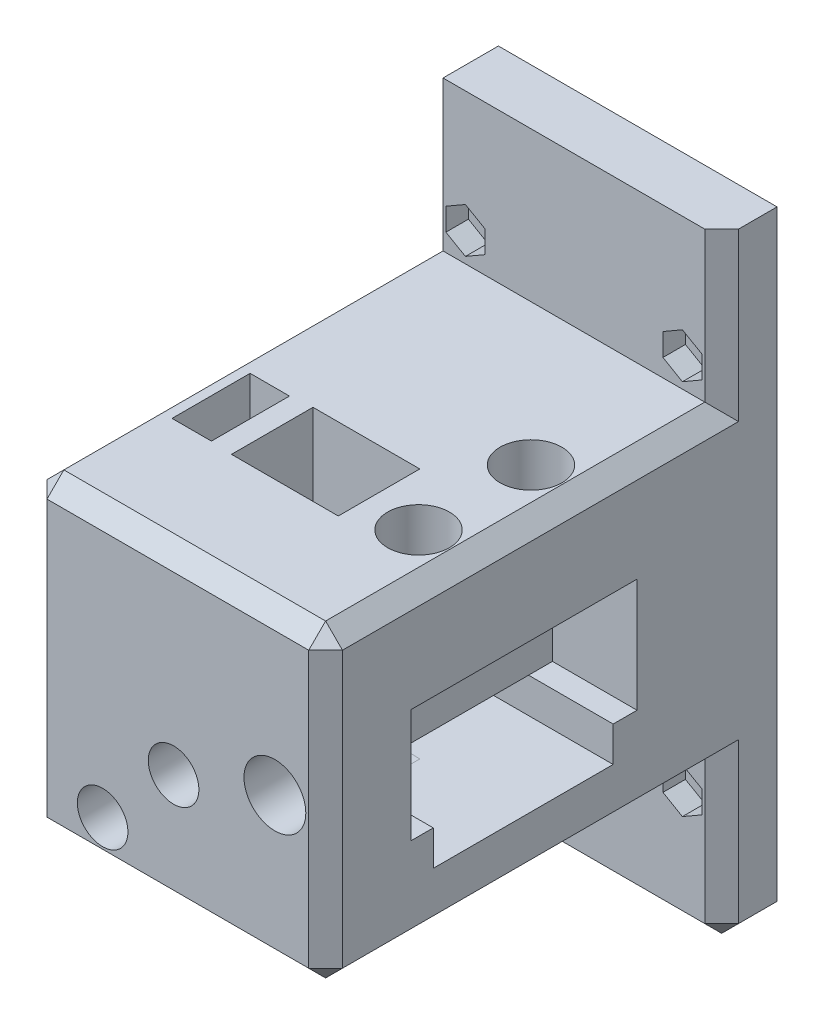
SolidWorks part; units mm, degrees
ref_plane "Front Plane" through (0, 0, 0) normal (1, 0, 0) x (0, 1, 0)
ref_plane "Top Plane" through (0, 0, 0) normal (0, 0, 1) x (0, 1, 0)
ref_plane "Right Plane" through (0, 0, 0) normal (0, 1, 0) x (-1, 0, 0)
sketch "Sketch1" plane through (0, 0, 0) normal (1, 0, 0) x (0, 1, 0)
  line L0 (-10.15, 6.7) -> (-10.15, -6.7)
  line L1 (-9.2, -7.65) -> (-8.5, -7.65)
  line L2 (-8.05, -7.2) -> (-8.05, -5.0949)
  line L3 (-6.8637, -4.6035) -> (-4.6847, -6.7825)
  line L4 (-3.85, -8.7978) -> (-3.85, -11.2022)
  line L5 (-4.6847, -13.2175) -> (-6.8637, -15.3965)
  line L6 (-8.05, -14.9051) -> (-8.05, -12.8)
  line L7 (-8.5, -12.35) -> (-9.2, -12.35)
  line L8 (-10.15, -13.3) -> (-10.15, -18)
  line L9 (-8, -20.15) -> (-3.3, -20.15)
  line L10 (-2.35, -19.2) -> (-2.35, -18.5)
  line L11 (-2.8, -18.05) -> (-4.9051, -18.05)
  line L12 (-5.3965, -16.8637) -> (-3.2175, -14.6847)
  line L13 (-1.2022, -13.85) -> (1.2022, -13.85)
  line L14 (3.2175, -14.6847) -> (5.3965, -16.8637)
  line L15 (4.9051, -18.05) -> (2.8, -18.05)
  line L16 (2.35, -18.5) -> (2.35, -19.2)
  line L17 (3.3, -20.15) -> (8, -20.15)
  line L18 (10.15, -18) -> (10.15, -13.3)
  line L19 (9.2, -12.35) -> (8.5, -12.35)
  line L20 (8.05, -12.8) -> (8.05, -14.9051)
  line L21 (6.8637, -15.3965) -> (4.6847, -13.2175)
  line L22 (3.85, -11.2022) -> (3.85, -8.7978)
  line L23 (4.6847, -6.7825) -> (6.8637, -4.6035)
  line L24 (8.05, -5.0949) -> (8.05, -7.2)
  line L25 (8.5, -7.65) -> (9.2, -7.65)
  line L26 (10.15, -6.7) -> (10.15, 6.7)
  line L27 (9.2, 7.65) -> (8.5, 7.65)
  line L28 (8.05, 7.2) -> (8.05, 5.0949)
  line L29 (6.8637, 4.6035) -> (4.6847, 6.7825)
  line L30 (3.85, 8.7978) -> (3.85, 11.2022)
  line L31 (4.6847, 13.2175) -> (6.8637, 15.3965)
  line L32 (8.05, 14.9051) -> (8.05, 12.8)
  line L33 (8.5, 12.35) -> (9.2, 12.35)
  line L34 (10.15, 13.3) -> (10.15, 18)
  line L35 (8, 20.15) -> (3.3, 20.15)
  line L36 (2.35, 19.2) -> (2.35, 18.5)
  line L37 (2.8, 18.05) -> (4.9051, 18.05)
  line L38 (5.3965, 16.8637) -> (3.2175, 14.6847)
  line L39 (1.2022, 13.85) -> (-1.2022, 13.85)
  line L40 (-3.2175, 14.6847) -> (-5.3965, 16.8637)
  line L41 (-4.9051, 18.05) -> (-2.8, 18.05)
  line L42 (-2.35, 18.5) -> (-2.35, 19.2)
  line L43 (-3.3, 20.15) -> (-8, 20.15)
  line L44 (-10.15, 18) -> (-10.15, 13.3)
  line L45 (-9.2, 12.35) -> (-8.5, 12.35)
  line L46 (-8.05, 12.8) -> (-8.05, 14.9051)
  line L47 (-6.8637, 15.3965) -> (-4.6847, 13.2175)
  line L48 (-3.85, 11.2022) -> (-3.85, 8.7978)
  line L49 (-4.6847, 6.7825) -> (-6.8637, 4.6035)
  line L50 (-8.05, 5.0949) -> (-8.05, 7.2)
  line L51 (-8.5, 7.65) -> (-9.2, 7.65)
  line L52 (-2.5, 18.5) -> (-2.5, 19.2)
  line L53 (-3.3, 20) -> (-8, 20)
  line L54 (-10, 18) -> (-10, 13.3)
  line L55 (-9.2, 12.5) -> (-8.5, 12.5)
  line L56 (-8.2, 12.8) -> (-8.2, 14.9051)
  line L57 (-6.7576, 15.5025) -> (-4.5787, 13.3236)
  line L58 (-3.7, 11.2022) -> (-3.7, 8.7978)
  line L59 (-4.5787, 6.6764) -> (-6.7576, 4.4975)
  line L60 (-8.2, 5.0949) -> (-8.2, 7.2)
  line L61 (-8.5, 7.5) -> (-9.2, 7.5)
  line L62 (-10, 6.7) -> (-10, -6.7)
  line L63 (-9.2, -7.5) -> (-8.5, -7.5)
  line L64 (-8.2, -7.2) -> (-8.2, -5.0949)
  line L65 (-6.7576, -4.4975) -> (-4.5787, -6.6764)
  line L66 (-3.7, -8.7978) -> (-3.7, -11.2022)
  line L67 (-4.5787, -13.3236) -> (-6.7576, -15.5025)
  line L68 (-8.2, -14.9051) -> (-8.2, -12.8)
  line L69 (-8.5, -12.5) -> (-9.2, -12.5)
  line L70 (-10, -13.3) -> (-10, -18)
  line L71 (-8, -20) -> (-3.3, -20)
  line L72 (-2.5, -19.2) -> (-2.5, -18.5)
  line L73 (-2.8, -18.2) -> (-4.9051, -18.2)
  line L74 (-5.5025, -16.7576) -> (-3.3236, -14.5787)
  line L75 (-1.2022, -13.7) -> (1.2022, -13.7)
  line L76 (3.3236, -14.5787) -> (5.5025, -16.7576)
  line L77 (4.9051, -18.2) -> (2.8, -18.2)
  line L78 (2.5, -18.5) -> (2.5, -19.2)
  line L79 (3.3, -20) -> (8, -20)
  line L80 (10, -18) -> (10, -13.3)
  line L81 (9.2, -12.5) -> (8.5, -12.5)
  line L82 (8.2, -12.8) -> (8.2, -14.9051)
  line L83 (6.7576, -15.5025) -> (4.5787, -13.3236)
  line L84 (3.7, -11.2022) -> (3.7, -8.7978)
  line L85 (4.5787, -6.6764) -> (6.7576, -4.4975)
  line L86 (8.2, -5.0949) -> (8.2, -7.2)
  line L87 (8.5, -7.5) -> (9.2, -7.5)
  line L88 (10, -6.7) -> (10, 6.7)
  line L89 (9.2, 7.5) -> (8.5, 7.5)
  line L90 (8.2, 7.2) -> (8.2, 5.0949)
  line L91 (6.7576, 4.4975) -> (4.5787, 6.6764)
  line L92 (3.7, 8.7978) -> (3.7, 11.2022)
  line L93 (4.5787, 13.3236) -> (6.7576, 15.5025)
  line L94 (8.2, 14.9051) -> (8.2, 12.8)
  line L95 (8.5, 12.5) -> (9.2, 12.5)
  line L96 (10, 13.3) -> (10, 18)
  line L97 (8, 20) -> (3.3, 20)
  line L98 (2.5, 19.2) -> (2.5, 18.5)
  line L99 (2.8, 18.2) -> (4.9051, 18.2)
  line L100 (5.5025, 16.7576) -> (3.3236, 14.5787)
  line L101 (1.2022, 13.7) -> (-1.2022, 13.7)
  line L102 (-3.3236, 14.5787) -> (-5.5025, 16.7576)
  line L103 (-4.9051, 18.2) -> (-2.8, 18.2)
  line L104 (-2.5, 18.5) -> (-2.5, 19.2)
  line L105 (-3.3, 20) -> (-8, 20)
  line L106 (-10, 18) -> (-10, 13.3)
  line L107 (-9.2, 12.5) -> (-8.5, 12.5)
  line L108 (-8.2, 12.8) -> (-8.2, 14.9051)
  line L109 (-6.7576, 15.5025) -> (-4.5787, 13.3236)
  line L110 (-3.7, 11.2022) -> (-3.7, 8.7978)
  line L111 (-4.5787, 6.6764) -> (-6.7576, 4.4975)
  line L112 (-8.2, 5.0949) -> (-8.2, 7.2)
  line L113 (-8.5, 7.5) -> (-9.2, 7.5)
  line L114 (-10, 6.7) -> (-10, -6.7)
  line L115 (-9.2, -7.5) -> (-8.5, -7.5)
  line L116 (-8.2, -7.2) -> (-8.2, -5.0949)
  line L117 (-6.7576, -4.4975) -> (-4.5787, -6.6764)
  line L118 (-3.7, -8.7978) -> (-3.7, -11.2022)
  line L119 (-4.5787, -13.3236) -> (-6.7576, -15.5025)
  line L120 (-8.2, -14.9051) -> (-8.2, -12.8)
  line L121 (-8.5, -12.5) -> (-9.2, -12.5)
  line L122 (-10, -13.3) -> (-10, -18)
  line L123 (-8, -20) -> (-3.3, -20)
  line L124 (-2.5, -19.2) -> (-2.5, -18.5)
  line L125 (-2.8, -18.2) -> (-4.9051, -18.2)
  line L126 (-5.5025, -16.7576) -> (-3.3236, -14.5787)
  line L127 (-1.2022, -13.7) -> (1.2022, -13.7)
  line L128 (3.3236, -14.5787) -> (5.5025, -16.7576)
  line L129 (4.9051, -18.2) -> (2.8, -18.2)
  line L130 (2.5, -18.5) -> (2.5, -19.2)
  line L131 (3.3, -20) -> (8, -20)
  line L132 (10, -18) -> (10, -13.3)
  line L133 (9.2, -12.5) -> (8.5, -12.5)
  line L134 (8.2, -12.8) -> (8.2, -14.9051)
  line L135 (6.7576, -15.5025) -> (4.5787, -13.3236)
  line L136 (3.7, -11.2022) -> (3.7, -8.7978)
  line L137 (4.5787, -6.6764) -> (6.7576, -4.4975)
  line L138 (8.2, -5.0949) -> (8.2, -7.2)
  line L139 (8.5, -7.5) -> (9.2, -7.5)
  line L140 (10, -6.7) -> (10, 6.7)
  line L141 (9.2, 7.5) -> (8.5, 7.5)
  line L142 (8.2, 7.2) -> (8.2, 5.0949)
  line L143 (6.7576, 4.4975) -> (4.5787, 6.6764)
  line L144 (3.7, 8.7978) -> (3.7, 11.2022)
  line L145 (4.5787, 13.3236) -> (6.7576, 15.5025)
  line L146 (8.2, 14.9051) -> (8.2, 12.8)
  line L147 (8.5, 12.5) -> (9.2, 12.5)
  line L148 (10, 13.3) -> (10, 18)
  line L149 (8, 20) -> (3.3, 20)
  line L150 (2.5, 19.2) -> (2.5, 18.5)
  line L151 (2.8, 18.2) -> (4.9051, 18.2)
  line L152 (5.5025, 16.7576) -> (3.3236, 14.5787)
  line L153 (1.2022, 13.7) -> (-1.2022, 13.7)
  line L154 (-3.3236, 14.5787) -> (-5.5025, 16.7576)
  line L155 (-4.9051, 18.2) -> (-2.8, 18.2)
  line L156 (55, -61.229) -> (55, -45) construction
  line L157 (17.15, 35.15) -> (-17.15, 35.15)
  line L158 (17.15, 35.15) -> (17.15, -35.15)
  line L159 (17.15, -35.15) -> (-17.15, -35.15)
  line L160 (-17.15, 35.15) -> (-17.15, -35.15)
  line L161 (17.15, 35.15) -> (-17.15, -35.15) construction
  line L162 (17.15, -35.15) -> (-17.15, 35.15) construction
  line L163 (-55, -45) -> (55, -45)
  line L164 (-55, -45) -> (-55, -35.15)
  line L165 (-55, -35.15) -> (55, -35.15)
  line L166 (55, -45) -> (55, -35.15)
  arc A0 (-10.15, -6.7) -> (-9.2, -7.65) centre (-9.2, -6.7) ccw
  arc A1 (-8.5, -7.65) -> (-8.05, -7.2) centre (-8.5, -7.2) ccw
  arc A2 (-6.8637, -4.6035) -> (-8.05, -5.0949) centre (-7.3551, -5.0949) ccw
  arc A3 (-3.85, -8.7978) -> (-4.6847, -6.7825) centre (-6.7, -8.7978) ccw
  arc A4 (-4.6847, -13.2175) -> (-3.85, -11.2022) centre (-6.7, -11.2022) ccw
  arc A5 (-8.05, -14.9051) -> (-6.8637, -15.3965) centre (-7.3551, -14.9051) ccw
  arc A6 (-8.05, -12.8) -> (-8.5, -12.35) centre (-8.5, -12.8) ccw
  arc A7 (-9.2, -12.35) -> (-10.15, -13.3) centre (-9.2, -13.3) ccw
  arc A8 (-10.15, -18) -> (-8, -20.15) centre (-8, -18) ccw
  arc A9 (-3.3, -20.15) -> (-2.35, -19.2) centre (-3.3, -19.2) ccw
  arc A10 (-2.35, -18.5) -> (-2.8, -18.05) centre (-2.8, -18.5) ccw
  arc A11 (-5.3965, -16.8637) -> (-4.9051, -18.05) centre (-4.9051, -17.3551) ccw
  arc A12 (-1.2022, -13.85) -> (-3.2175, -14.6847) centre (-1.2022, -16.7) ccw
  arc A13 (3.2175, -14.6847) -> (1.2022, -13.85) centre (1.2022, -16.7) ccw
  arc A14 (4.9051, -18.05) -> (5.3965, -16.8637) centre (4.9051, -17.3551) ccw
  arc A15 (2.8, -18.05) -> (2.35, -18.5) centre (2.8, -18.5) ccw
  arc A16 (2.35, -19.2) -> (3.3, -20.15) centre (3.3, -19.2) ccw
  arc A17 (8, -20.15) -> (10.15, -18) centre (8, -18) ccw
  arc A18 (10.15, -13.3) -> (9.2, -12.35) centre (9.2, -13.3) ccw
  arc A19 (8.5, -12.35) -> (8.05, -12.8) centre (8.5, -12.8) ccw
  arc A20 (6.8637, -15.3965) -> (8.05, -14.9051) centre (7.3551, -14.9051) ccw
  arc A21 (3.85, -11.2022) -> (4.6847, -13.2175) centre (6.7, -11.2022) ccw
  arc A22 (4.6847, -6.7825) -> (3.85, -8.7978) centre (6.7, -8.7978) ccw
  arc A23 (8.05, -5.0949) -> (6.8637, -4.6035) centre (7.3551, -5.0949) ccw
  arc A24 (8.05, -7.2) -> (8.5, -7.65) centre (8.5, -7.2) ccw
  arc A25 (9.2, -7.65) -> (10.15, -6.7) centre (9.2, -6.7) ccw
  arc A26 (10.15, 6.7) -> (9.2, 7.65) centre (9.2, 6.7) ccw
  arc A27 (8.5, 7.65) -> (8.05, 7.2) centre (8.5, 7.2) ccw
  arc A28 (6.8637, 4.6035) -> (8.05, 5.0949) centre (7.3551, 5.0949) ccw
  arc A29 (3.85, 8.7978) -> (4.6847, 6.7825) centre (6.7, 8.7978) ccw
  arc A30 (4.6847, 13.2175) -> (3.85, 11.2022) centre (6.7, 11.2022) ccw
  arc A31 (8.05, 14.9051) -> (6.8637, 15.3965) centre (7.3551, 14.9051) ccw
  arc A32 (8.05, 12.8) -> (8.5, 12.35) centre (8.5, 12.8) ccw
  arc A33 (9.2, 12.35) -> (10.15, 13.3) centre (9.2, 13.3) ccw
  arc A34 (10.15, 18) -> (8, 20.15) centre (8, 18) ccw
  arc A35 (3.3, 20.15) -> (2.35, 19.2) centre (3.3, 19.2) ccw
  arc A36 (2.35, 18.5) -> (2.8, 18.05) centre (2.8, 18.5) ccw
  arc A37 (5.3965, 16.8637) -> (4.9051, 18.05) centre (4.9051, 17.3551) ccw
  arc A38 (1.2022, 13.85) -> (3.2175, 14.6847) centre (1.2022, 16.7) ccw
  arc A39 (-3.2175, 14.6847) -> (-1.2022, 13.85) centre (-1.2022, 16.7) ccw
  arc A40 (-4.9051, 18.05) -> (-5.3965, 16.8637) centre (-4.9051, 17.3551) ccw
  arc A41 (-2.8, 18.05) -> (-2.35, 18.5) centre (-2.8, 18.5) ccw
  arc A42 (-2.35, 19.2) -> (-3.3, 20.15) centre (-3.3, 19.2) ccw
  arc A43 (-8, 20.15) -> (-10.15, 18) centre (-8, 18) ccw
  arc A44 (-10.15, 13.3) -> (-9.2, 12.35) centre (-9.2, 13.3) ccw
  arc A45 (-8.5, 12.35) -> (-8.05, 12.8) centre (-8.5, 12.8) ccw
  arc A46 (-6.8637, 15.3965) -> (-8.05, 14.9051) centre (-7.3551, 14.9051) ccw
  arc A47 (-3.85, 11.2022) -> (-4.6847, 13.2175) centre (-6.7, 11.2022) ccw
  arc A48 (-4.6847, 6.7825) -> (-3.85, 8.7978) centre (-6.7, 8.7978) ccw
  arc A49 (-8.05, 5.0949) -> (-6.8637, 4.6035) centre (-7.3551, 5.0949) ccw
  arc A50 (-8.05, 7.2) -> (-8.5, 7.65) centre (-8.5, 7.2) ccw
  arc A51 (-9.2, 7.65) -> (-10.15, 6.7) centre (-9.2, 6.7) ccw
  arc A52 (-2.8, 18.2) -> (-2.5, 18.5) centre (-2.8, 18.5) ccw
  arc A53 (-2.5, 19.2) -> (-3.3, 20) centre (-3.3, 19.2) ccw
  arc A54 (-8, 20) -> (-10, 18) centre (-8, 18) ccw
  arc A55 (-10, 13.3) -> (-9.2, 12.5) centre (-9.2, 13.3) ccw
  arc A56 (-8.5, 12.5) -> (-8.2, 12.8) centre (-8.5, 12.8) ccw
  arc A57 (-6.7576, 15.5025) -> (-8.2, 14.9051) centre (-7.3551, 14.9051) ccw
  arc A58 (-3.7, 11.2022) -> (-4.5787, 13.3236) centre (-6.7, 11.2022) ccw
  arc A59 (-4.5787, 6.6764) -> (-3.7, 8.7978) centre (-6.7, 8.7978) ccw
  arc A60 (-8.2, 5.0949) -> (-6.7576, 4.4975) centre (-7.3551, 5.0949) ccw
  arc A61 (-8.2, 7.2) -> (-8.5, 7.5) centre (-8.5, 7.2) ccw
  arc A62 (-9.2, 7.5) -> (-10, 6.7) centre (-9.2, 6.7) ccw
  arc A63 (-10, -6.7) -> (-9.2, -7.5) centre (-9.2, -6.7) ccw
  arc A64 (-8.5, -7.5) -> (-8.2, -7.2) centre (-8.5, -7.2) ccw
  arc A65 (-6.7576, -4.4975) -> (-8.2, -5.0949) centre (-7.3551, -5.0949) ccw
  arc A66 (-3.7, -8.7978) -> (-4.5787, -6.6764) centre (-6.7, -8.7978) ccw
  arc A67 (-4.5787, -13.3236) -> (-3.7, -11.2022) centre (-6.7, -11.2022) ccw
  arc A68 (-8.2, -14.9051) -> (-6.7576, -15.5025) centre (-7.3551, -14.9051) ccw
  arc A69 (-8.2, -12.8) -> (-8.5, -12.5) centre (-8.5, -12.8) ccw
  arc A70 (-9.2, -12.5) -> (-10, -13.3) centre (-9.2, -13.3) ccw
  arc A71 (-10, -18) -> (-8, -20) centre (-8, -18) ccw
  arc A72 (-3.3, -20) -> (-2.5, -19.2) centre (-3.3, -19.2) ccw
  arc A73 (-2.5, -18.5) -> (-2.8, -18.2) centre (-2.8, -18.5) ccw
  arc A74 (-5.5025, -16.7576) -> (-4.9051, -18.2) centre (-4.9051, -17.3551) ccw
  arc A75 (-1.2022, -13.7) -> (-3.3236, -14.5787) centre (-1.2022, -16.7) ccw
  arc A76 (3.3236, -14.5787) -> (1.2022, -13.7) centre (1.2022, -16.7) ccw
  arc A77 (4.9051, -18.2) -> (5.5025, -16.7576) centre (4.9051, -17.3551) ccw
  arc A78 (2.8, -18.2) -> (2.5, -18.5) centre (2.8, -18.5) ccw
  arc A79 (2.5, -19.2) -> (3.3, -20) centre (3.3, -19.2) ccw
  arc A80 (8, -20) -> (10, -18) centre (8, -18) ccw
  arc A81 (10, -13.3) -> (9.2, -12.5) centre (9.2, -13.3) ccw
  arc A82 (8.5, -12.5) -> (8.2, -12.8) centre (8.5, -12.8) ccw
  arc A83 (6.7576, -15.5025) -> (8.2, -14.9051) centre (7.3551, -14.9051) ccw
  arc A84 (3.7, -11.2022) -> (4.5787, -13.3236) centre (6.7, -11.2022) ccw
  arc A85 (4.5787, -6.6764) -> (3.7, -8.7978) centre (6.7, -8.7978) ccw
  arc A86 (8.2, -5.0949) -> (6.7576, -4.4975) centre (7.3551, -5.0949) ccw
  arc A87 (8.2, -7.2) -> (8.5, -7.5) centre (8.5, -7.2) ccw
  arc A88 (9.2, -7.5) -> (10, -6.7) centre (9.2, -6.7) ccw
  arc A89 (10, 6.7) -> (9.2, 7.5) centre (9.2, 6.7) ccw
  arc A90 (8.5, 7.5) -> (8.2, 7.2) centre (8.5, 7.2) ccw
  arc A91 (6.7576, 4.4975) -> (8.2, 5.0949) centre (7.3551, 5.0949) ccw
  arc A92 (3.7, 8.7978) -> (4.5787, 6.6764) centre (6.7, 8.7978) ccw
  arc A93 (4.5787, 13.3236) -> (3.7, 11.2022) centre (6.7, 11.2022) ccw
  arc A94 (8.2, 14.9051) -> (6.7576, 15.5025) centre (7.3551, 14.9051) ccw
  arc A95 (8.2, 12.8) -> (8.5, 12.5) centre (8.5, 12.8) ccw
  arc A96 (9.2, 12.5) -> (10, 13.3) centre (9.2, 13.3) ccw
  arc A97 (10, 18) -> (8, 20) centre (8, 18) ccw
  arc A98 (3.3, 20) -> (2.5, 19.2) centre (3.3, 19.2) ccw
  arc A99 (2.5, 18.5) -> (2.8, 18.2) centre (2.8, 18.5) ccw
  arc A100 (5.5025, 16.7576) -> (4.9051, 18.2) centre (4.9051, 17.3551) ccw
  arc A101 (1.2022, 13.7) -> (3.3236, 14.5787) centre (1.2022, 16.7) ccw
  arc A102 (-3.3236, 14.5787) -> (-1.2022, 13.7) centre (-1.2022, 16.7) ccw
  arc A103 (-4.9051, 18.2) -> (-5.5025, 16.7576) centre (-4.9051, 17.3551) ccw
  arc A104 (-2.8, 18.2) -> (-2.5, 18.5) centre (-2.8, 18.5) ccw
  arc A105 (-2.5, 19.2) -> (-3.3, 20) centre (-3.3, 19.2) ccw
  arc A106 (-8, 20) -> (-10, 18) centre (-8, 18) ccw
  arc A107 (-10, 13.3) -> (-9.2, 12.5) centre (-9.2, 13.3) ccw
  arc A108 (-8.5, 12.5) -> (-8.2, 12.8) centre (-8.5, 12.8) ccw
  arc A109 (-6.7576, 15.5025) -> (-8.2, 14.9051) centre (-7.3551, 14.9051) ccw
  arc A110 (-3.7, 11.2022) -> (-4.5787, 13.3236) centre (-6.7, 11.2022) ccw
  arc A111 (-4.5787, 6.6764) -> (-3.7, 8.7978) centre (-6.7, 8.7978) ccw
  arc A112 (-8.2, 5.0949) -> (-6.7576, 4.4975) centre (-7.3551, 5.0949) ccw
  arc A113 (-8.2, 7.2) -> (-8.5, 7.5) centre (-8.5, 7.2) ccw
  arc A114 (-9.2, 7.5) -> (-10, 6.7) centre (-9.2, 6.7) ccw
  arc A115 (-10, -6.7) -> (-9.2, -7.5) centre (-9.2, -6.7) ccw
  arc A116 (-8.5, -7.5) -> (-8.2, -7.2) centre (-8.5, -7.2) ccw
  arc A117 (-6.7576, -4.4975) -> (-8.2, -5.0949) centre (-7.3551, -5.0949) ccw
  arc A118 (-3.7, -8.7978) -> (-4.5787, -6.6764) centre (-6.7, -8.7978) ccw
  arc A119 (-4.5787, -13.3236) -> (-3.7, -11.2022) centre (-6.7, -11.2022) ccw
  arc A120 (-8.2, -14.9051) -> (-6.7576, -15.5025) centre (-7.3551, -14.9051) ccw
  arc A121 (-8.2, -12.8) -> (-8.5, -12.5) centre (-8.5, -12.8) ccw
  arc A122 (-9.2, -12.5) -> (-10, -13.3) centre (-9.2, -13.3) ccw
  arc A123 (-10, -18) -> (-8, -20) centre (-8, -18) ccw
  arc A124 (-3.3, -20) -> (-2.5, -19.2) centre (-3.3, -19.2) ccw
  arc A125 (-2.5, -18.5) -> (-2.8, -18.2) centre (-2.8, -18.5) ccw
  arc A126 (-5.5025, -16.7576) -> (-4.9051, -18.2) centre (-4.9051, -17.3551) ccw
  arc A127 (-1.2022, -13.7) -> (-3.3236, -14.5787) centre (-1.2022, -16.7) ccw
  arc A128 (3.3236, -14.5787) -> (1.2022, -13.7) centre (1.2022, -16.7) ccw
  arc A129 (4.9051, -18.2) -> (5.5025, -16.7576) centre (4.9051, -17.3551) ccw
  arc A130 (2.8, -18.2) -> (2.5, -18.5) centre (2.8, -18.5) ccw
  arc A131 (2.5, -19.2) -> (3.3, -20) centre (3.3, -19.2) ccw
  arc A132 (8, -20) -> (10, -18) centre (8, -18) ccw
  arc A133 (10, -13.3) -> (9.2, -12.5) centre (9.2, -13.3) ccw
  arc A134 (8.5, -12.5) -> (8.2, -12.8) centre (8.5, -12.8) ccw
  arc A135 (6.7576, -15.5025) -> (8.2, -14.9051) centre (7.3551, -14.9051) ccw
  arc A136 (3.7, -11.2022) -> (4.5787, -13.3236) centre (6.7, -11.2022) ccw
  arc A137 (4.5787, -6.6764) -> (3.7, -8.7978) centre (6.7, -8.7978) ccw
  arc A138 (8.2, -5.0949) -> (6.7576, -4.4975) centre (7.3551, -5.0949) ccw
  arc A139 (8.2, -7.2) -> (8.5, -7.5) centre (8.5, -7.2) ccw
  arc A140 (9.2, -7.5) -> (10, -6.7) centre (9.2, -6.7) ccw
  arc A141 (10, 6.7) -> (9.2, 7.5) centre (9.2, 6.7) ccw
  arc A142 (8.5, 7.5) -> (8.2, 7.2) centre (8.5, 7.2) ccw
  arc A143 (6.7576, 4.4975) -> (8.2, 5.0949) centre (7.3551, 5.0949) ccw
  arc A144 (3.7, 8.7978) -> (4.5787, 6.6764) centre (6.7, 8.7978) ccw
  arc A145 (4.5787, 13.3236) -> (3.7, 11.2022) centre (6.7, 11.2022) ccw
  arc A146 (8.2, 14.9051) -> (6.7576, 15.5025) centre (7.3551, 14.9051) ccw
  arc A147 (8.2, 12.8) -> (8.5, 12.5) centre (8.5, 12.8) ccw
  arc A148 (9.2, 12.5) -> (10, 13.3) centre (9.2, 13.3) ccw
  arc A149 (10, 18) -> (8, 20) centre (8, 18) ccw
  arc A150 (3.3, 20) -> (2.5, 19.2) centre (3.3, 19.2) ccw
  arc A151 (2.5, 18.5) -> (2.8, 18.2) centre (2.8, 18.5) ccw
  arc A152 (5.5025, 16.7576) -> (4.9051, 18.2) centre (4.9051, 17.3551) ccw
  arc A153 (1.2022, 13.7) -> (3.3236, 14.5787) centre (1.2022, 16.7) ccw
  arc A154 (-3.3236, 14.5787) -> (-1.2022, 13.7) centre (-1.2022, 16.7) ccw
  arc A155 (-4.9051, 18.2) -> (-5.5025, 16.7576) centre (-4.9051, 17.3551) ccw
  point P312 (0, 0)
  dimension "D3" = 7
  dimension "D4" = 15
  dimension "D1" = 0
  dimension "D2" = 0.15
extrude "Boss-Extrude1" add sketch "Sketch1" against normal up to surface (15.0483 mm away) contours L157 L160 L159 L158 A51 L51 A50 L50 A49 L49 A48 L48 A47 L47 A46 L46 A45 L45 A44 L44 A43 L43 A42 L42 A41 L41 A40 L40 A39 L39 A38 L38 A37 L37 A36 L36 A35 L35 A34 L34 A33 L33 A32 L32 A31 L31 A30 L30 A29 L29 | L163 L166 L165 L159 L164 region at (0, 16.3678, 0) region at (0, 0, -40.075)
sketch "Sketch2" plane through (0, 0, 0) normal (1, 0, 0) x (0, 1, 0)
  line L8 (17.15, 35.15) -> (-17.15, 35.15)
  line L9 (-17.15, 35.15) -> (-17.15, -35.15)
  line L10 (-17.15, -35.15) -> (-55, -35.15)
  line L11 (-55, -35.15) -> (-55, -45)
  line L12 (-55, -45) -> (55, -45)
  line L13 (55, -45) -> (55, -35.15)
  line L14 (55, -35.15) -> (17.15, -35.15)
  line L15 (17.15, -35.15) -> (17.15, 35.15)
  line L16 (17.15, 35.15) -> (-17.15, 35.15)
  line L17 (-17.15, 35.15) -> (-17.15, -35.15)
  line L18 (-17.15, -35.15) -> (-55, -35.15)
  line L19 (-55, -35.15) -> (-55, -45)
  line L20 (-55, -45) -> (55, -45)
  line L21 (55, -45) -> (55, -35.15)
  line L22 (55, -35.15) -> (17.15, -35.15)
  line L23 (17.15, -35.15) -> (17.15, 35.15)
  dimension "D1" = 0
extrude "Boss-Extrude3" add sketch "Sketch2" along normal blind 10
sketch "Sketch3" plane through (10, 0, 0) normal (1, 0, 0) x (0, 1, 0)
  line L0 (-17.15, -35.15) -> (17.15, -35.15)
  line L8 (17.15, -35.15) -> (17.15, 35.15)
  line L9 (17.15, 35.15) -> (-17.15, 35.15)
  line L10 (-17.15, 35.15) -> (-17.15, -35.15)
  line L11 (-17.15, -35.15) -> (-55, -35.15)
  line L12 (-55, -35.15) -> (-55, -45)
  line L13 (-55, -45) -> (55, -45)
  line L14 (55, -45) -> (55, -35.15)
  line L15 (55, -35.15) -> (17.15, -35.15)
  line L16 (17.15, -35.15) -> (17.15, 35.15)
  line L17 (17.15, 35.15) -> (-17.15, 35.15)
  line L18 (-17.15, 35.15) -> (-17.15, -35.15)
  line L19 (-17.15, -35.15) -> (-55, -35.15)
  line L20 (-55, -35.15) -> (-55, -45)
  line L21 (-55, -45) -> (55, -45)
  line L22 (55, -45) -> (55, -35.15)
  line L23 (55, -35.15) -> (17.15, -35.15)
  line M13 (-17.15, -35.15) -> (-55, -35.15)
  line M14 (-55, -35.15) -> (-55, -45)
  line M15 (-55, -45) -> (55, -45)
  line M16 (55, -45) -> (55, -35.15)
  line M17 (55, -35.15) -> (17.15, -35.15)
  dimension "D1" = 0
extrude "Boss-Extrude4" add sketch "Sketch3" along normal up to surface (27.5183 mm away) contours L0 M13 M14 M15 M16 M17 region at (10, 0, -40.075)
sketch "Sketch4" plane through (0, 0, -35.15) normal (0, 0, 1) x (1, 0, 0)
  circle A1 centre (-8.0682, 33.5) radius 2 construction
  circle A2 centre (-8.0682, -33.5) radius 2 construction
  circle A5 centre (-8.0682, 33.5) radius 2
  circle A6 centre (-8.0682, -33.5) radius 2
  circle A9 centre (30.5382, -33.5) radius 2 construction
  circle A10 centre (30.5382, 33.5) radius 2 construction
  circle A11 centre (30.5382, -33.5) radius 2
  circle A12 centre (30.5382, 33.5) radius 2
extrude "Cut-Extrude1" cut sketch "Sketch4" against normal through all both and the other way through all
mirror "Mirror1" [suppressed] of bodies 107
delete or keep bodies "Body-Delete/Keep 1" [suppressed] type delete bodies bodies 107
sketch "Sketch8" plane through (10, 0, 0) normal (1, 0, 0) x (0, 1, 0)
  line L1 (-74.9038, 48.4779) -> (55, 48.4779)
  line L2 (-74.9038, 48.4779) -> (-74.9038, -35.15)
  line L3 (-74.9038, -35.15) -> (55, -35.15)
  line L4 (55, 48.4779) -> (55, -35.15)
extrude "Cut-Extrude3" cut sketch "Sketch8" against normal through all both and the other way through all
sketch "Sketch9" plane through (-15.0483, 0, 0) normal (-1, 0, 0) x (0, -1, 0)
  line L0 (-0.849, 35.304) -> (-13.028, 35.304) construction
  line L1 (-10, 20) -> (10, 20)
  line L2 (-10, 20) -> (-10, -20)
  line L3 (-10, -20) -> (10, -20)
  line L4 (10, 20) -> (10, -20)
  line L5 (-23.028, 35.304) -> (21.33, 35.304)
  line L6 (-23.028, 35.304) -> (-23.028, -35.304)
  line L7 (-23.028, -35.304) -> (21.33, -35.304)
  line L8 (21.33, 35.304) -> (21.33, -35.304)
  line L9 (-13.028, 35.304) -> (-13.028, 21.3438) construction
  line L52 (2.8, 18.2) -> (4.9051, 18.2)
  line L53 (5.5025, 16.7576) -> (3.3236, 14.5787)
  line L54 (1.2022, 13.7) -> (-1.2022, 13.7)
  line L55 (-3.3236, 14.5787) -> (-5.5025, 16.7576)
  line L56 (-4.9051, 18.2) -> (-2.8, 18.2)
  line L57 (-2.5, 18.5) -> (-2.5, 19.2)
  line L58 (-3.3, 20) -> (-8, 20)
  line L59 (-10, 18) -> (-10, 13.3)
  line L60 (-9.2, 12.5) -> (-8.5, 12.5)
  line L61 (-8.2, 12.8) -> (-8.2, 14.9051)
  line L62 (-6.7576, 15.5025) -> (-4.5787, 13.3236)
  line L63 (-3.7, 11.2022) -> (-3.7, 8.7978)
  line L64 (-4.5787, 6.6764) -> (-6.7576, 4.4975)
  line L65 (-8.2, 5.0949) -> (-8.2, 7.2)
  line L66 (-8.5, 7.5) -> (-9.2, 7.5)
  line L67 (-10, 6.7) -> (-10, -6.7)
  line L68 (-9.2, -7.5) -> (-8.5, -7.5)
  line L69 (-8.2, -7.2) -> (-8.2, -5.0949)
  line L70 (-6.7576, -4.4975) -> (-4.5787, -6.6764)
  line L71 (-3.7, -8.7978) -> (-3.7, -11.2022)
  line L72 (-4.5787, -13.3236) -> (-6.7576, -15.5025)
  line L73 (-8.2, -14.9051) -> (-8.2, -12.8)
  line L74 (-8.5, -12.5) -> (-9.2, -12.5)
  line L75 (-10, -13.3) -> (-10, -18)
  line L76 (-8, -20) -> (-3.3, -20)
  line L77 (-2.5, -19.2) -> (-2.5, -18.5)
  line L78 (-2.8, -18.2) -> (-4.9051, -18.2)
  line L79 (-5.5025, -16.7576) -> (-3.3236, -14.5787)
  line L80 (-1.2022, -13.7) -> (1.2022, -13.7)
  line L81 (3.3236, -14.5787) -> (5.5025, -16.7576)
  line L82 (4.9051, -18.2) -> (2.8, -18.2)
  line L83 (2.5, -18.5) -> (2.5, -19.2)
  line L84 (3.3, -20) -> (8, -20)
  line L85 (10, -18) -> (10, -13.3)
  line L86 (9.2, -12.5) -> (8.5, -12.5)
  line L87 (8.2, -12.8) -> (8.2, -14.9051)
  line L88 (6.7576, -15.5025) -> (4.5787, -13.3236)
  line L89 (3.7, -11.2022) -> (3.7, -8.7978)
  line L90 (4.5787, -6.6764) -> (6.7576, -4.4975)
  line L91 (8.2, -5.0949) -> (8.2, -7.2)
  line L92 (8.5, -7.5) -> (9.2, -7.5)
  line L93 (10, -6.7) -> (10, 6.7)
  line L94 (9.2, 7.5) -> (8.5, 7.5)
  line L95 (8.2, 7.2) -> (8.2, 5.0949)
  line L96 (6.7576, 4.4975) -> (4.5787, 6.6764)
  line L97 (3.7, 8.7978) -> (3.7, 11.2022)
  line L98 (4.5787, 13.3236) -> (6.7576, 15.5025)
  line L99 (8.2, 14.9051) -> (8.2, 12.8)
  line L100 (8.5, 12.5) -> (9.2, 12.5)
  line L101 (10, 13.3) -> (10, 18)
  line L102 (8, 20) -> (3.3, 20)
  line L103 (2.5, 19.2) -> (2.5, 18.5)
  line L104 (2.8, 18.2) -> (4.9051, 18.2)
  line L105 (5.5025, 16.7576) -> (3.3236, 14.5787)
  line L106 (1.2022, 13.7) -> (-1.2022, 13.7)
  line L107 (-3.3236, 14.5787) -> (-5.5025, 16.7576)
  line L108 (-4.9051, 18.2) -> (-2.8, 18.2)
  line L109 (-2.5, 18.5) -> (-2.5, 19.2)
  line L110 (-3.3, 20) -> (-8, 20)
  line L111 (-10, 18) -> (-10, 13.3)
  line L112 (-9.2, 12.5) -> (-8.5, 12.5)
  line L113 (-8.2, 12.8) -> (-8.2, 14.9051)
  line L114 (-6.7576, 15.5025) -> (-4.5787, 13.3236)
  line L115 (-3.7, 11.2022) -> (-3.7, 8.7978)
  line L116 (-4.5787, 6.6764) -> (-6.7576, 4.4975)
  line L117 (-8.2, 5.0949) -> (-8.2, 7.2)
  line L118 (-8.5, 7.5) -> (-9.2, 7.5)
  line L119 (-10, 6.7) -> (-10, -6.7)
  line L120 (-9.2, -7.5) -> (-8.5, -7.5)
  line L121 (-8.2, -7.2) -> (-8.2, -5.0949)
  line L122 (-6.7576, -4.4975) -> (-4.5787, -6.6764)
  line L123 (-3.7, -8.7978) -> (-3.7, -11.2022)
  line L124 (-4.5787, -13.3236) -> (-6.7576, -15.5025)
  line L125 (-8.2, -14.9051) -> (-8.2, -12.8)
  line L126 (-8.5, -12.5) -> (-9.2, -12.5)
  line L127 (-10, -13.3) -> (-10, -18)
  line L128 (-8, -20) -> (-3.3, -20)
  line L129 (-2.5, -19.2) -> (-2.5, -18.5)
  line L130 (-2.8, -18.2) -> (-4.9051, -18.2)
  line L131 (-5.5025, -16.7576) -> (-3.3236, -14.5787)
  line L132 (-1.2022, -13.7) -> (1.2022, -13.7)
  line L133 (3.3236, -14.5787) -> (5.5025, -16.7576)
  line L134 (4.9051, -18.2) -> (2.8, -18.2)
  line L135 (2.5, -18.5) -> (2.5, -19.2)
  line L136 (3.3, -20) -> (8, -20)
  line L137 (10, -18) -> (10, -13.3)
  line L138 (9.2, -12.5) -> (8.5, -12.5)
  line L139 (8.2, -12.8) -> (8.2, -14.9051)
  line L140 (6.7576, -15.5025) -> (4.5787, -13.3236)
  line L141 (3.7, -11.2022) -> (3.7, -8.7978)
  line L142 (4.5787, -6.6764) -> (6.7576, -4.4975)
  line L143 (8.2, -5.0949) -> (8.2, -7.2)
  line L144 (8.5, -7.5) -> (9.2, -7.5)
  line L145 (10, -6.7) -> (10, 6.7)
  line L146 (9.2, 7.5) -> (8.5, 7.5)
  line L147 (8.2, 7.2) -> (8.2, 5.0949)
  line L148 (6.7576, 4.4975) -> (4.5787, 6.6764)
  line L149 (3.7, 8.7978) -> (3.7, 11.2022)
  line L150 (4.5787, 13.3236) -> (6.7576, 15.5025)
  line L151 (8.2, 14.9051) -> (8.2, 12.8)
  line L152 (8.5, 12.5) -> (9.2, 12.5)
  line L153 (10, 13.3) -> (10, 18)
  line L154 (8, 20) -> (3.3, 20)
  line L155 (2.5, 19.2) -> (2.5, 18.5)
  arc A52 (2.5, 18.5) -> (2.8, 18.2) centre (2.8, 18.5) ccw
  arc A53 (5.5025, 16.7576) -> (4.9051, 18.2) centre (4.9051, 17.3551) ccw
  arc A54 (1.2022, 13.7) -> (3.3236, 14.5787) centre (1.2022, 16.7) ccw
  arc A55 (-3.3236, 14.5787) -> (-1.2022, 13.7) centre (-1.2022, 16.7) ccw
  arc A56 (-4.9051, 18.2) -> (-5.5025, 16.7576) centre (-4.9051, 17.3551) ccw
  arc A57 (-2.8, 18.2) -> (-2.5, 18.5) centre (-2.8, 18.5) ccw
  arc A58 (-2.5, 19.2) -> (-3.3, 20) centre (-3.3, 19.2) ccw
  arc A59 (-8, 20) -> (-10, 18) centre (-8, 18) ccw
  arc A60 (-10, 13.3) -> (-9.2, 12.5) centre (-9.2, 13.3) ccw
  arc A61 (-8.5, 12.5) -> (-8.2, 12.8) centre (-8.5, 12.8) ccw
  arc A62 (-6.7576, 15.5025) -> (-8.2, 14.9051) centre (-7.3551, 14.9051) ccw
  arc A63 (-3.7, 11.2022) -> (-4.5787, 13.3236) centre (-6.7, 11.2022) ccw
  arc A64 (-4.5787, 6.6764) -> (-3.7, 8.7978) centre (-6.7, 8.7978) ccw
  arc A65 (-8.2, 5.0949) -> (-6.7576, 4.4975) centre (-7.3551, 5.0949) ccw
  arc A66 (-8.2, 7.2) -> (-8.5, 7.5) centre (-8.5, 7.2) ccw
  arc A67 (-9.2, 7.5) -> (-10, 6.7) centre (-9.2, 6.7) ccw
  arc A68 (-10, -6.7) -> (-9.2, -7.5) centre (-9.2, -6.7) ccw
  arc A69 (-8.5, -7.5) -> (-8.2, -7.2) centre (-8.5, -7.2) ccw
  arc A70 (-6.7576, -4.4975) -> (-8.2, -5.0949) centre (-7.3551, -5.0949) ccw
  arc A71 (-3.7, -8.7978) -> (-4.5787, -6.6764) centre (-6.7, -8.7978) ccw
  arc A72 (-4.5787, -13.3236) -> (-3.7, -11.2022) centre (-6.7, -11.2022) ccw
  arc A73 (-8.2, -14.9051) -> (-6.7576, -15.5025) centre (-7.3551, -14.9051) ccw
  arc A74 (-8.2, -12.8) -> (-8.5, -12.5) centre (-8.5, -12.8) ccw
  arc A75 (-9.2, -12.5) -> (-10, -13.3) centre (-9.2, -13.3) ccw
  arc A76 (-10, -18) -> (-8, -20) centre (-8, -18) ccw
  arc A77 (-3.3, -20) -> (-2.5, -19.2) centre (-3.3, -19.2) ccw
  arc A78 (-2.5, -18.5) -> (-2.8, -18.2) centre (-2.8, -18.5) ccw
  arc A79 (-5.5025, -16.7576) -> (-4.9051, -18.2) centre (-4.9051, -17.3551) ccw
  arc A80 (-1.2022, -13.7) -> (-3.3236, -14.5787) centre (-1.2022, -16.7) ccw
  arc A81 (3.3236, -14.5787) -> (1.2022, -13.7) centre (1.2022, -16.7) ccw
  arc A82 (4.9051, -18.2) -> (5.5025, -16.7576) centre (4.9051, -17.3551) ccw
  arc A83 (2.8, -18.2) -> (2.5, -18.5) centre (2.8, -18.5) ccw
  arc A84 (2.5, -19.2) -> (3.3, -20) centre (3.3, -19.2) ccw
  arc A85 (8, -20) -> (10, -18) centre (8, -18) ccw
  arc A86 (10, -13.3) -> (9.2, -12.5) centre (9.2, -13.3) ccw
  arc A87 (8.5, -12.5) -> (8.2, -12.8) centre (8.5, -12.8) ccw
  arc A88 (6.7576, -15.5025) -> (8.2, -14.9051) centre (7.3551, -14.9051) ccw
  arc A89 (3.7, -11.2022) -> (4.5787, -13.3236) centre (6.7, -11.2022) ccw
  arc A90 (4.5787, -6.6764) -> (3.7, -8.7978) centre (6.7, -8.7978) ccw
  arc A91 (8.2, -5.0949) -> (6.7576, -4.4975) centre (7.3551, -5.0949) ccw
  arc A92 (8.2, -7.2) -> (8.5, -7.5) centre (8.5, -7.2) ccw
  arc A93 (9.2, -7.5) -> (10, -6.7) centre (9.2, -6.7) ccw
  arc A94 (10, 6.7) -> (9.2, 7.5) centre (9.2, 6.7) ccw
  arc A95 (8.5, 7.5) -> (8.2, 7.2) centre (8.5, 7.2) ccw
  arc A96 (6.7576, 4.4975) -> (8.2, 5.0949) centre (7.3551, 5.0949) ccw
  arc A97 (3.7, 8.7978) -> (4.5787, 6.6764) centre (6.7, 8.7978) ccw
  arc A98 (4.5787, 13.3236) -> (3.7, 11.2022) centre (6.7, 11.2022) ccw
  arc A99 (8.2, 14.9051) -> (6.7576, 15.5025) centre (7.3551, 14.9051) ccw
  arc A100 (8.2, 12.8) -> (8.5, 12.5) centre (8.5, 12.8) ccw
  arc A101 (9.2, 12.5) -> (10, 13.3) centre (9.2, 13.3) ccw
  arc A102 (10, 18) -> (8, 20) centre (8, 18) ccw
  arc A103 (3.3, 20) -> (2.5, 19.2) centre (3.3, 19.2) ccw
  arc A104 (2.5, 18.5) -> (2.8, 18.2) centre (2.8, 18.5) ccw
  arc A105 (5.5025, 16.7576) -> (4.9051, 18.2) centre (4.9051, 17.3551) ccw
  arc A106 (1.2022, 13.7) -> (3.3236, 14.5787) centre (1.2022, 16.7) ccw
  arc A107 (-3.3236, 14.5787) -> (-1.2022, 13.7) centre (-1.2022, 16.7) ccw
  arc A108 (-4.9051, 18.2) -> (-5.5025, 16.7576) centre (-4.9051, 17.3551) ccw
  arc A109 (-2.8, 18.2) -> (-2.5, 18.5) centre (-2.8, 18.5) ccw
  arc A110 (-2.5, 19.2) -> (-3.3, 20) centre (-3.3, 19.2) ccw
  arc A111 (-8, 20) -> (-10, 18) centre (-8, 18) ccw
  arc A112 (-10, 13.3) -> (-9.2, 12.5) centre (-9.2, 13.3) ccw
  arc A113 (-8.5, 12.5) -> (-8.2, 12.8) centre (-8.5, 12.8) ccw
  arc A114 (-6.7576, 15.5025) -> (-8.2, 14.9051) centre (-7.3551, 14.9051) ccw
  arc A115 (-3.7, 11.2022) -> (-4.5787, 13.3236) centre (-6.7, 11.2022) ccw
  arc A116 (-4.5787, 6.6764) -> (-3.7, 8.7978) centre (-6.7, 8.7978) ccw
  arc A117 (-8.2, 5.0949) -> (-6.7576, 4.4975) centre (-7.3551, 5.0949) ccw
  arc A118 (-8.2, 7.2) -> (-8.5, 7.5) centre (-8.5, 7.2) ccw
  arc A119 (-9.2, 7.5) -> (-10, 6.7) centre (-9.2, 6.7) ccw
  arc A120 (-10, -6.7) -> (-9.2, -7.5) centre (-9.2, -6.7) ccw
  arc A121 (-8.5, -7.5) -> (-8.2, -7.2) centre (-8.5, -7.2) ccw
  arc A122 (-6.7576, -4.4975) -> (-8.2, -5.0949) centre (-7.3551, -5.0949) ccw
  arc A123 (-3.7, -8.7978) -> (-4.5787, -6.6764) centre (-6.7, -8.7978) ccw
  arc A124 (-4.5787, -13.3236) -> (-3.7, -11.2022) centre (-6.7, -11.2022) ccw
  arc A125 (-8.2, -14.9051) -> (-6.7576, -15.5025) centre (-7.3551, -14.9051) ccw
  arc A126 (-8.2, -12.8) -> (-8.5, -12.5) centre (-8.5, -12.8) ccw
  arc A127 (-9.2, -12.5) -> (-10, -13.3) centre (-9.2, -13.3) ccw
  arc A128 (-10, -18) -> (-8, -20) centre (-8, -18) ccw
  arc A129 (-3.3, -20) -> (-2.5, -19.2) centre (-3.3, -19.2) ccw
  arc A130 (-2.5, -18.5) -> (-2.8, -18.2) centre (-2.8, -18.5) ccw
  arc A131 (-5.5025, -16.7576) -> (-4.9051, -18.2) centre (-4.9051, -17.3551) ccw
  arc A132 (-1.2022, -13.7) -> (-3.3236, -14.5787) centre (-1.2022, -16.7) ccw
  arc A133 (3.3236, -14.5787) -> (1.2022, -13.7) centre (1.2022, -16.7) ccw
  arc A134 (4.9051, -18.2) -> (5.5025, -16.7576) centre (4.9051, -17.3551) ccw
  arc A135 (2.8, -18.2) -> (2.5, -18.5) centre (2.8, -18.5) ccw
  arc A136 (2.5, -19.2) -> (3.3, -20) centre (3.3, -19.2) ccw
  arc A137 (8, -20) -> (10, -18) centre (8, -18) ccw
  arc A138 (10, -13.3) -> (9.2, -12.5) centre (9.2, -13.3) ccw
  arc A139 (8.5, -12.5) -> (8.2, -12.8) centre (8.5, -12.8) ccw
  arc A140 (6.7576, -15.5025) -> (8.2, -14.9051) centre (7.3551, -14.9051) ccw
  arc A141 (3.7, -11.2022) -> (4.5787, -13.3236) centre (6.7, -11.2022) ccw
  arc A142 (4.5787, -6.6764) -> (3.7, -8.7978) centre (6.7, -8.7978) ccw
  arc A143 (8.2, -5.0949) -> (6.7576, -4.4975) centre (7.3551, -5.0949) ccw
  arc A144 (8.2, -7.2) -> (8.5, -7.5) centre (8.5, -7.2) ccw
  arc A145 (9.2, -7.5) -> (10, -6.7) centre (9.2, -6.7) ccw
  arc A146 (10, 6.7) -> (9.2, 7.5) centre (9.2, 6.7) ccw
  arc A147 (8.5, 7.5) -> (8.2, 7.2) centre (8.5, 7.2) ccw
  arc A148 (6.7576, 4.4975) -> (8.2, 5.0949) centre (7.3551, 5.0949) ccw
  arc A149 (3.7, 8.7978) -> (4.5787, 6.6764) centre (6.7, 8.7978) ccw
  arc A150 (4.5787, 13.3236) -> (3.7, 11.2022) centre (6.7, 11.2022) ccw
  arc A151 (8.2, 14.9051) -> (6.7576, 15.5025) centre (7.3551, 14.9051) ccw
  arc A152 (8.2, 12.8) -> (8.5, 12.5) centre (8.5, 12.8) ccw
  arc A153 (9.2, 12.5) -> (10, 13.3) centre (9.2, 13.3) ccw
  arc A154 (10, 18) -> (8, 20) centre (8, 18) ccw
  arc A155 (3.3, 20) -> (2.5, 19.2) centre (3.3, 19.2) ccw
  point P20 (5.65, -20)
  dimension "D2" = 10
  dimension "D1" = 0
extrude "Boss-Extrude5" add sketch "Sketch9" against normal up to surface (15.0483 mm away) contours L6 L5 L8 L7 | L2 L1 L4 L3
sketch "Sketch10" plane through (0, 0, 0) normal (1, 0, 0) x (0, 1, 0)
  line L0 (10, -20) -> (-10, -20) construction
  line L1 (10, 20) -> (10, -20) construction
  line L2 (10, 20) -> (-10, 20) construction
  line L3 (-10, 20) -> (-10, -20) construction
  line L12 (10, -20) -> (-10, -20)
  line L13 (10, 20) -> (10, -20)
  line L14 (10, 20) -> (-10, 20)
  line L15 (-10, 20) -> (-10, -20)
  line L16 (10.1, 20.1) -> (10.1, -20.1)
  line L17 (10.1, -20.1) -> (-10.1, -20.1)
  line L18 (-10.1, 20.1) -> (-10.1, -20.1)
  line L19 (10.1, 20.1) -> (-10.1, 20.1)
  dimension "D2" = 0.1
extrude "Cut-Extrude6" cut sketch "Sketch10" against normal through all contours L12 L15 L14 L13 | L16 L17 L18 L19
sketch "Sketch11" plane through (0, 0, 35.304) normal (0, 0, 1) x (1, 0, 0)
  line L0 (0, -1.2022) -> (-12.0483, 1.2022) construction
  line L2 (-15.0483, 23.028) -> (-15.0483, -21.33) construction
  line L4 (0, -1.2022) -> (0, 1.2022)
  line L5 (0, 1.2022) -> (-580.53, 1.2022)
  line L6 (-580.53, 1.2022) -> (-580.53, -1.2022)
  line L7 (-580.53, -1.2022) -> (0, -1.2022)
  line L8 (0, -1.2022) -> (0, 1.2022) construction
  line L9 (0, 1.2022) -> (-580.53, 1.2022) construction
  line L10 (-580.53, 1.2022) -> (-580.53, -1.2022) construction
  line L11 (-580.53, -1.2022) -> (0, -1.2022) construction
  circle A0 centre (-6.0241, 0) radius 3
  dimension "D2" = 6
  dimension "D3" = 3
  dimension "D1" = 0
extrude "Cut-Extrude7" cut sketch "Sketch11" against normal blind 30
sketch "Sketch12" plane through (0, 0, 35.304) normal (0, 0, 1) x (1, 0, 0)
  circle A0 centre (-6.0241, 0) radius 5.5
  dimension "D1" = 11
extrude "Cut-Extrude8" cut sketch "Sketch12" against normal blind 8 and the other way through all
sketch "Sketch14" plane through (0, 0, 0) normal (1, 0, 0) x (0, 1, 0)
  line L0 (-11.23, 16.15) -> (-26.23, 16.15) construction
  line L1 (-16.33, 16.15) -> (-9.2978, 16.15)
  line L2 (-16.33, 16.15) -> (-16.33, -15.85)
  line L3 (-16.33, -15.85) -> (-9.2978, -15.85)
  line L4 (-9.2978, 16.15) -> (-9.2978, -15.85)
  line L5 (-21.33, 35.304) -> (-21.33, -35.15) construction
  dimension "D1" = 5
  dimension "D2" = 32
extrude "Cut-Extrude10" cut sketch "Sketch14" against normal through all both and the other way through all
sketch "Sketch19" plane through (0, 0, 0) normal (1, 0, 0) x (0, 1, 0)
  line L2 (-10.1, 16.15) -> (-10.1, -15.85)
  line L4 (-21.33, -35.15) -> (23.028, -35.15)
  line L5 (23.028, -35.15) -> (23.028, 35.304)
  line L6 (23.028, 35.304) -> (-21.33, 35.304)
  line L7 (-21.33, 35.304) -> (-21.33, -35.15)
  line L8 (-21.33, -35.15) -> (23.028, -35.15)
  line L9 (23.028, -35.15) -> (23.028, 35.304)
  line L10 (23.028, 35.304) -> (-21.33, 35.304)
  line L11 (-21.33, 35.304) -> (-21.33, -35.15)
  line L13 (-16.33, 16.15) -> (-10.1, 16.15)
  line L14 (-16.33, 16.15) -> (-16.33, -15.85)
  line L15 (-16.33, -15.85) -> (-10.1, -15.85)
  line L16 (-10.1, 16.15) -> (-10.1, -15.85)
  line M5 (-16.33, 16.15) -> (-10.1, 16.15)
  line M6 (-10.1, 16.15) -> (-10.1, 20.1)
  line M7 (-10.1, 20.1) -> (10.1, 20.1)
  line M8 (10.1, 20.1) -> (10.1, -20.1)
  line M9 (10.1, -20.1) -> (-10.1, -20.1)
  line M10 (-10.1, -20.1) -> (-10.1, -15.85)
  line M11 (-10.1, -15.85) -> (-16.33, -15.85)
  line M12 (-16.33, -15.85) -> (-16.33, 16.15)
  line M13 (-21.33, -35.15) -> (23.028, -35.15)
  line M14 (23.028, -35.15) -> (23.028, 35.304)
  line M15 (23.028, 35.304) -> (-21.33, 35.304)
  line M16 (-21.33, 35.304) -> (-21.33, -35.15)
  dimension "D1" = 0
extrude "Boss-Extrude9" add sketch "Sketch19" along normal blind 3 contours M16 M13 M14 M15 M12 M5 M6 M7 M8 M9 M10 M11 | L2 M6 M10 M9 M8 M7 region at (0, 0, 0) region at (0, -20.4975, 0.077)
sketch "Sketch15" plane through (0, 0, -35.15) normal (0, 0, 1) x (1, 0, 0)
  line L0 (-15.0483, 0.849) -> (37.5183, 0.849) construction
  line L1 (-15.0483, 23.028) -> (-15.0483, -21.33) construction
  line L2 (37.5183, 55) -> (37.5183, -55) construction
  line L4 (-15.0483, 28.349) -> (37.5183, 28.349)
  line L5 (-15.0483, 28.349) -> (-15.0483, -26.651)
  line L6 (-15.0483, -26.651) -> (37.5183, -26.651)
  line L7 (37.5183, 28.349) -> (37.5183, -26.651)
  line L8 (-15.0483, 28.349) -> (37.5183, -26.651) construction
  line L9 (-15.0483, -26.651) -> (37.5183, 28.349) construction
  line L10 (-15.0483, -21.33) -> (3, -21.33)
  line L11 (-15.0483, -21.33) -> (-15.0483, 23.028)
  line L12 (-15.0483, 23.028) -> (3, 23.028)
  line L13 (3, -21.33) -> (3, 23.028)
  line L14 (3, 23.028) -> (-15.0483, 23.028) construction
  line L15 (3, 23.028) -> (3, -21.33) construction
  point P6 (11.235, 0.849)
  line M13 (3, -21.33) -> (-15.0483, -21.33)
  line M14 (-15.0483, -21.33) -> (-15.0483, -55)
  line M16 (37.5183, -55) -> (37.5183, 55)
  line M18 (-15.0483, 55) -> (-15.0483, 23.028)
  line M19 (-15.0483, 23.028) -> (3, 23.028)
  dimension "D1" = 55
extrude "Boss-Extrude6" add sketch "Sketch15" along normal up to surface (19.3 mm away) contours L6 L4 M14 M16 M18 M19 M13 region at (17.8444, 0.849, -35.15) up to face at (-4.8193, -12.592, -15.85)
sketch "Sketch16" plane through (0, 0, -15.85) normal (0, 0, 1) x (1, 0, 0)
  circle A0 centre (24.73, -18.73) radius 3.4
  point P3 (0, 0)
  point P4 (0, 0)
  point P5 (24.73, -18.73)
  dimension "D1" = 6.8
extrude "Boss-Extrude7" add sketch "Sketch16" along normal blind 2.1
sketch "Sketch18" plane through (0, 0, -15.85) normal (0, 0, 1) x (1, 0, 0)
  line L0 (3, -10.1) -> (24.0914, -8.7504)
  line L2 (0, -10.1) -> (3, -10.1)
  line L3 (-15.0483, -16.33) -> (14.73, -16.33)
  line L4 (14.73, -16.33) -> (14.73, -26.651)
  line L5 (37.5183, -26.651) -> (-15.0483, -26.651) construction
  line L6 (14.73, -26.651) -> (18.6261, -26.651)
  line L7 (34.73, -18.73) -> (34.73, -26.651)
  line L9 (3, 23.028) -> (-15.0483, 23.028) construction
  line L10 (-15.0483, 28.349) -> (37.5183, 28.349)
  line L11 (-15.0483, 28.349) -> (-15.0483, -26.651)
  line L12 (-15.0483, -26.651) -> (37.5183, -26.651)
  line L13 (-15.0483, -16.33) -> (3, -16.33)
  line L14 (3, -16.33) -> (3, -21.33)
  line L15 (3, -21.33) -> (-15.0483, -21.33)
  line L16 (-15.0483, -21.33) -> (-15.0483, -26.651)
  line L17 (-15.0483, -26.651) -> (37.5183, -26.651)
  line L18 (37.5183, -26.651) -> (37.5183, 28.349)
  line L19 (37.5183, 28.349) -> (-15.0483, 28.349)
  line L20 (-15.0483, 28.349) -> (-15.0483, 23.028)
  line L21 (-15.0483, 23.028) -> (3, 23.028)
  line L22 (37.5183, 28.349) -> (37.5183, -26.651)
  line L23 (3, 23.028) -> (3, -10.1)
  line L24 (0, -10.1) -> (-15.0483, -10.1)
  line L25 (-15.0483, -10.1) -> (-15.0483, -16.33)
  line L37 (0, -10.1) -> (-15.0483, -10.1)
  line L38 (-15.0483, -10.1) -> (-15.0483, -16.33)
  line L39 (-15.0483, -21.33) -> (3, -21.33)
  line L40 (-15.0483, -21.33) -> (-15.0483, 23.028)
  line L41 (-15.0483, 23.028) -> (3, 23.028)
  line L42 (3, -21.33) -> (3, 23.028)
  line L43 (3, 23.028) -> (3, -21.33) construction
  line L44 (3, -10.1) -> (0, -10.1)
  line L45 (3, -10.1) -> (0, -10.1)
  circle A1 centre (24.73, -18.73) radius 10 construction
  circle A2 centre (24.73, -18.73) radius 10
  line M21 (3, -21.33) -> (-15.0483, -21.33)
  line M22 (-15.0483, -21.33) -> (-15.0483, -26.651)
  line M23 (-15.0483, -26.651) -> (37.5183, -26.651)
  line M24 (37.5183, -26.651) -> (37.5183, 28.349)
  line M25 (37.5183, 28.349) -> (-15.0483, 28.349)
  line M26 (-15.0483, 28.349) -> (-15.0483, 23.028)
  line M27 (-15.0483, 23.028) -> (3, 23.028)
  line M46 (3, -16.33) -> (3, -21.33)
  line M47 (3, 23.028) -> (3, -10.1)
  dimension "D2" = 20
  dimension "D3" = 6.23
  dimension "D1" = 0
extrude "Boss-Extrude8" add sketch "Sketch18" along normal blind 16.35 contours L4 L3 M46 M21 M22 M23 | A2 L7 L0 M23 M24 M25 M26 M27 M47 region at (19.153, 9.4172, -15.85) region at (2.2787, -22.5964, -15.85)
sketch "Sketch20" plane through (0, 0, 0.5) normal (0, 0, 1) x (1, 0, 0)
  circle A0 centre (12, -6) radius 3.4
  point P3 (0, 0)
  point P4 (12, -6)
  dimension "D1" = 6.8
extrude "Boss-Extrude10" add sketch "Sketch20" along normal blind 0.5
sketch "Sketch21" plane through (0, 0, 0.5) normal (0, 0, 1) x (1, 0, 0)
  line L0 (22, -6) -> (22, 28.349)
  line L5 (-15.0483, 28.349) -> (37.5183, 28.349)
  line L6 (-15.0483, 28.349) -> (-15.0483, -26.651)
  line L7 (-15.0483, -26.651) -> (37.5183, -26.651)
  line L8 (37.5183, 28.349) -> (37.5183, -26.651)
  line L9 (-15.0483, 23.028) -> (3, 23.028)
  line L10 (-15.0483, 23.028) -> (-15.0483, -21.33)
  line L11 (-15.0483, -21.33) -> (3, -21.33)
  line L12 (3, 23.028) -> (3, -21.33)
  line L13 (-15.0483, -10.1) -> (3, -10.1)
  line L14 (-15.0483, -10.1) -> (-15.0483, -16.33)
  line L15 (-15.0483, -16.33) -> (3, -16.33)
  line L24 (3, -10.1) -> (3, -16.33)
  line L25 (3, -16.33) -> (12, -16)
  line L28 (3, 23.028) -> (3, 28.349)
  circle A1 centre (12, -6) radius 10
  line M22 (-15.0483, 28.349) -> (-15.0483, 23.028)
  line M23 (34.73, -26.651) -> (37.5183, -26.651)
  line M24 (37.5183, -26.651) -> (37.5183, 28.349)
  line M25 (37.5183, 28.349) -> (-15.0483, 28.349)
  arc M51 (24.0914, -8.7504) -> (34.73, -18.73) centre (24.73, -18.73) cw
  line M52 (34.73, -18.73) -> (34.73, -26.651)
  line M53 (-15.0483, 23.028) -> (3, 23.028)
  line M54 (3, -10.1) -> (24.0914, -8.7504)
  dimension "D1" = 20
extrude "Boss-Extrude11" add sketch "Sketch21" along normal blind 14.5 contours L28 L5 M53 M22 | A1 L0 M54 M51 M52 M23 M24 M25 | L15 L6 L11 L12 | A1 L25 L12 L11 L6 L7 M52 M51 M54 region at (30.3341, 6.9817, 0.5) region at (15.4956, -20.3765, 0.5) region at (-6.0241, 25.6885, 0.5) region at (-6.0241, -18.83, 0.5)
sketch "Sketch24" plane through (0, 0, 0.5) normal (0, 0, -1) x (0, 1, 0)
  circle A1 centre (-18.73, 24.73) radius 3.4
  circle A2 centre (-18.73, 24.73) radius 3.4
  dimension "D1" = 0
extrude "Boss-Extrude12" add sketch "Sketch24" along normal blind 0.5
sketch "Sketch25" plane through (0, 0, -13.75) normal (0, 0, 1) x (1, 0, 0)
  circle A1 centre (24.73, -18.73) radius 3.4
  circle A2 centre (24.73, -18.73) radius 3.4
  dimension "D1" = 0
extrude "Cut-Extrude11" cut sketch "Sketch25" against normal blind 0.25
ref_plane "Plane3" through (0, 0, 14) normal (0, 0, 1) x (0, -1, 0)
sketch "Sketch26" plane through (0, 0, 14) normal (0, 0, 1) x (0, -1, 0)
  circle A1 centre (6, 12) radius 3.4
  circle A2 centre (6, 12) radius 3.4
  dimension "D1" = 0
extrude "Boss-Extrude13" add sketch "Sketch26" along normal blind 1 separate body
sketch "Sketch27" plane through (0, 0, 15) normal (0, 0, 1) x (1, 0, 0)
  line L1 (-15.0483, -26.651) -> (37.5183, -26.651)
  line L2 (-15.0483, -26.651) -> (-15.0483, 28.349)
  line L3 (-15.0483, 28.349) -> (37.5183, 28.349)
  line L4 (37.5183, -26.651) -> (37.5183, 28.349)
  line L5 (-15.0483, -21.33) -> (3, -21.33)
  line L6 (-15.0483, -21.33) -> (-15.0483, 23.028)
  line L7 (-15.0483, 23.028) -> (3, 23.028)
  line L8 (3, -21.33) -> (3, 23.028)
  line M5 (3, -21.33) -> (-15.0483, -21.33)
  line M6 (-15.0483, -21.33) -> (-15.0483, -26.651)
  line M7 (-15.0483, -26.651) -> (37.5183, -26.651)
  line M8 (37.5183, -26.651) -> (37.5183, 28.349)
  line M9 (37.5183, 28.349) -> (22, 28.349)
  line M10 (22, 28.349) -> (22, -6)
  arc M11 (22, -6) -> (12, -16) centre (12, -6) cw
  line M12 (12, -16) -> (3, -16.33)
  line M13 (3, -16.33) -> (3, -21.33)
extrude "Boss-Extrude14" add sketch "Sketch27" along normal up to surface (20.304 mm away) contours M13 M5 M6 M7 M8 M9 M10 M11 M12 | L8 L3 L2 L7 M12 M11 M10 region at (23.6934, -5.262, 15) region at (10.3833, 8.6442, 15) up to face at (-6.0241, 0.849, 35.304)
chamfer "Chamfer1" distance 3 angle 45 16 edges at (-15.0483, 41.6745, -35.15) (-15.0483, 28.349, 0.077) (11.235, 28.349, 35.304) (-15.0483, 0.849, 35.304) (11.235, -26.651, 35.304) (-15.0483, -26.651, 0.077) (-15.0483, -40.8255, -35.15) (-15.0483, -55, -40.075) (11.235, -55, -35.15) (37.5183, 55, -40.075) (37.5183, 41.6745, -35.15) (37.5183, 28.349, 0.077) (37.5183, 0.849, 35.304) (37.5183, -26.651, 0.077) (37.5183, -40.8255, -35.15) (37.5183, -55, -40.075)
sketch "Sketch28" plane through (0, 0, -35.15) normal (0, 0, 1) x (1, 0, 0)
  line L1 (-8.0682, -37.5) -> (-4.6041, -35.5)
  line L2 (-4.6041, -35.5) -> (-4.6041, -31.5)
  line L3 (-4.6041, -31.5) -> (-8.0682, -29.5)
  line L4 (-8.0682, -29.5) -> (-11.5323, -31.5)
  line L5 (-11.5323, -31.5) -> (-11.5323, -35.5)
  line L6 (-11.5323, -35.5) -> (-8.0682, -37.5)
  line L7 (34.0023, -31.5) -> (30.5382, -29.5)
  line L8 (30.5382, -29.5) -> (27.0741, -31.5)
  line L9 (27.0741, -31.5) -> (27.0741, -35.5)
  line L10 (27.0741, -35.5) -> (30.5382, -37.5)
  line L11 (30.5382, -37.5) -> (34.0023, -35.5)
  line L12 (34.0023, -35.5) -> (34.0023, -31.5)
  line L25 (-4.6041, 31.5) -> (-4.6041, 35.5)
  line L26 (-4.6041, 35.5) -> (-8.0682, 37.5)
  line L27 (-8.0682, 37.5) -> (-11.5323, 35.5)
  line L28 (-11.5323, 35.5) -> (-11.5323, 31.5)
  line L29 (-11.5323, 31.5) -> (-8.0682, 29.5)
  line L30 (-8.0682, 29.5) -> (-4.6041, 31.5)
  line L31 (34.0023, 35.5) -> (30.5382, 37.5)
  line L32 (30.5382, 37.5) -> (27.0741, 35.5)
  line L33 (27.0741, 35.5) -> (27.0741, 31.5)
  line L34 (27.0741, 31.5) -> (30.5382, 29.5)
  line L35 (30.5382, 29.5) -> (34.0023, 31.5)
  line L36 (34.0023, 31.5) -> (34.0023, 35.5)
  circle A0 centre (-8.0682, -33.5) radius 3.4641 construction
  circle A1 centre (30.5382, -33.5) radius 3.4641 construction
  circle A2 centre (-8.0682, 33.5) radius 3.4641 construction
  circle A3 centre (30.5382, 33.5) radius 3.4641 construction
  dimension "D1" = 8
extrude "Cut-Extrude12" cut sketch "Sketch28" against normal blind 4
sketch "Sketch29" plane through (0, 28.349, 0) normal (0, 1, 0) x (-1, 0, 0)
  line L0 (0, 11.2022) -> (12.5483, 8.7978) construction
  line L1 (15.0483, 32.304) -> (15.0483, -38.15) construction
  line L2 (0, -8.7978) -> (12.5483, -11.2022) construction
  line L12 (0, 11.2022) -> (0, 8.7978)
  line L13 (0, 8.7978) -> (580.53, 8.7978)
  line L14 (580.53, 8.7978) -> (580.53, 11.2022)
  line L15 (580.53, 11.2022) -> (0, 11.2022)
  line L16 (0, 11.2022) -> (0, 8.7978) construction
  line L17 (0, 8.7978) -> (580.53, 8.7978) construction
  line L18 (580.53, 8.7978) -> (580.53, 11.2022) construction
  line L19 (580.53, 11.2022) -> (0, 11.2022) construction
  line L20 (0, -8.7978) -> (0, -11.2022)
  line L21 (0, -11.2022) -> (580.53, -11.2022)
  line L22 (580.53, -11.2022) -> (580.53, -8.7978)
  line L23 (580.53, -8.7978) -> (0, -8.7978)
  line L24 (0, -8.7978) -> (0, -11.2022) construction
  line L25 (0, -11.2022) -> (580.53, -11.2022) construction
  line L26 (580.53, -11.2022) -> (580.53, -8.7978) construction
  line L27 (580.53, -8.7978) -> (0, -8.7978) construction
  circle A0 centre (6.2741, 10) radius 5.5
  circle A1 centre (6.2741, -10) radius 5.5
  dimension "D5" = 11
  dimension "D1" = 2.5
  dimension "D4" = 2.5
  dimension "D2" = 0
  dimension "D3" = 0
extrude "Cut-Extrude13" cut sketch "Sketch29" against normal blind 8
sketch "Sketch30" plane through (0, 20.349, 0) normal (0, 1, 0) x (-1, 0, 0)
  circle A0 centre (6.2741, 10) radius 3
  circle A1 centre (6.2741, -10) radius 3
  dimension "D1" = 6
extrude "Cut-Extrude14" cut sketch "Sketch30" against normal blind 26
ref_plane "Plane2" through (-290.2667, 0, 0) normal (1, 0, 0) x (0, 1, 0)
mirror "Mirror2" about plane through (-290.2667, 0, 0) normal (1, 0, 0) of bodies 152 142
sketch "Sketch31" plane through (0, 28.349, 0) normal (0, 1, 0) x (-1, 0, 0)
  line L0 (613.36, 13.25) -> (613.36, 14.75) construction
  line L1 (613.36, 14.75) -> (606.3568, 14.75)
  line L2 (613.36, 14.75) -> (613.36, 0.8631)
  line L3 (613.36, 0.8631) -> (606.3568, 0.8631)
  line L4 (606.3568, 14.75) -> (606.3568, 0.8631)
  line L5 (613.36, 14.75) -> (597.36, 14.75) construction
  line L7 (-130.6895, 67.4324) -> (61.7699, 67.4324)
  line L8 (-130.6895, 67.4324) -> (-130.6895, -129.8926)
  line L9 (-130.6895, -129.8926) -> (61.7699, -129.8926)
  line L10 (61.7699, 67.4324) -> (61.7699, -129.8926)
extrude "Cut-Extrude15" cut sketch "Sketch31" against normal through all both and the other way through all contours L10 L7 L8 L9 | L1 L4 L3 L2 region at (-609.8584, 28.349, 7.8066) region at (34.4598, 28.349, -31.2301)
sketch "Sketch32" plane through (0, 0, 35.304) normal (0, 0, 1) x (1, 0, 0)
  circle A1 centre (-592.5335, -6) radius 2.5
  circle A2 centre (-592.5335, -6) radius 2.5
  circle A3 centre (-605.2635, -18.73) radius 2.5
  circle A4 centre (-605.2635, -18.73) radius 2.5
  dimension "D1" = 0
  dimension "D2" = 0
extrude "Cut-Extrude16" cut sketch "Sketch32" against normal through all both and the other way through all
sketch "Sketch33" plane through (0, 0, 35.304) normal (0, 0, 1) x (1, 0, 0)
  circle A0 centre (-605.1488, -18.75) radius 4.5
  dimension "D1" = 9
extrude "Cut-Extrude17" cut sketch "Sketch33" against normal blind 16 and the other way through all
sketch "Sketch34" plane through (0, 0, 35.304) normal (0, 0, 1) x (1, 0, 0)
  circle A0 centre (-592.53, -5.9) radius 4.5
  dimension "D1" = 9
extrude "Cut-Extrude18" cut sketch "Sketch34" against normal blind 12
sketch "Sketch35" plane through (0, 0, -45) normal (0, 0, -1) x (1, 0, 0)
  line L1 (-590.1585, 1.8864) -> (-587.7835, 6)
  line L2 (-587.7835, 6) -> (-590.1585, 10.1136)
  line L3 (-590.1585, 10.1136) -> (-594.9085, 10.1136)
  line L4 (-594.9085, 10.1136) -> (-597.2835, 6)
  line L5 (-597.2835, 6) -> (-594.9085, 1.8864)
  line L6 (-594.9085, 1.8864) -> (-590.1585, 1.8864)
  line L7 (-600.5135, 18.73) -> (-602.8885, 22.8436)
  line L8 (-602.8885, 22.8436) -> (-607.6385, 22.8436)
  line L9 (-607.6385, 22.8436) -> (-610.0135, 18.73)
  line L10 (-610.0135, 18.73) -> (-607.6385, 14.6164)
  line L11 (-607.6385, 14.6164) -> (-602.8885, 14.6164)
  line L12 (-602.8885, 14.6164) -> (-600.5135, 18.73)
  circle A0 centre (-592.5335, 6) radius 4.1136 construction
  circle A1 centre (-605.2635, 18.73) radius 4.1136 construction
  dimension "D1" = 4.75
extrude "Cut-Extrude19" cut sketch "Sketch35" against normal blind 20
sketch "Sketch36" plane through (0, 0, -25) normal (0, 0, -1) x (1, 0, 0)
  line L6 (-594.9085, 1.8864) -> (-590.1585, 1.8864)
  line L7 (-590.1585, 1.8864) -> (-587.7835, 6)
  line L8 (-587.7835, 6) -> (-590.1585, 10.1136)
  line L9 (-590.1585, 10.1136) -> (-594.9085, 10.1136)
  line L10 (-594.9085, 10.1136) -> (-597.2835, 6)
  line L11 (-597.2835, 6) -> (-594.9085, 1.8864)
  line L12 (-594.9085, 1.8864) -> (-590.1585, 1.8864)
  line L13 (-590.1585, 1.8864) -> (-587.7835, 6)
  line L14 (-587.7835, 6) -> (-590.1585, 10.1136)
  line L15 (-590.1585, 10.1136) -> (-594.9085, 10.1136)
  line L16 (-594.9085, 10.1136) -> (-597.2835, 6)
  line L17 (-597.2835, 6) -> (-594.9085, 1.8864)
  dimension "D1" = 0
extrude "Cut-Extrude20" cut sketch "Sketch36" against normal blind 13
